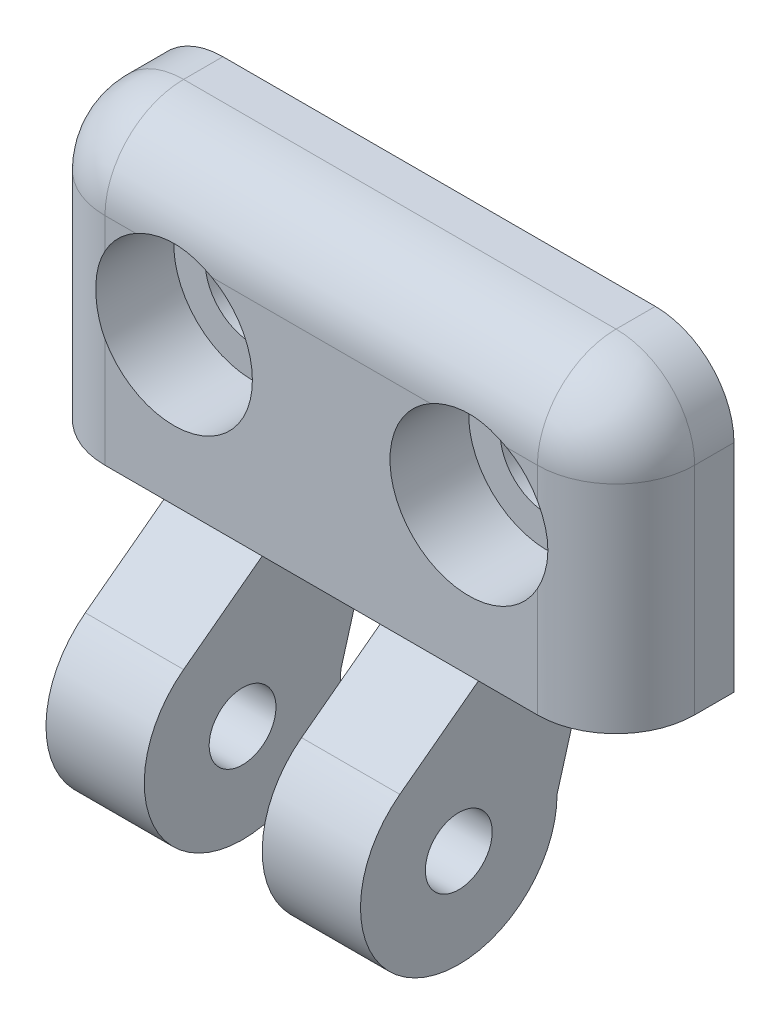
SolidWorks part; units mm, degrees
ref_plane "Front Plane" through (0, 0, 0) normal (0, 0, 1) x (1, 0, 0)
ref_plane "Top Plane" through (0, 0, 0) normal (0, 1, 0) x (1, 0, 0)
ref_plane "Right Plane" through (0, 0, 0) normal (1, 0, 0) x (0, 0, -1)
sketch "Sketch2" plane through (0, 0, 0) normal (0, 0, 1) x (1, 0, 0)
  line L1 (0, 0) -> (30, 0)
  line L2 (0, 0) -> (0, 15)
  line L3 (0, 15) -> (30, 15)
  line L4 (30, 0) -> (30, 15)
  dimension "D1" = 15
  dimension "D2" = 30
extrude "Boss-Extrude1" add sketch "Sketch2" along normal blind 6
hole_wizard "CBORE for M4 SHCS1" positions "Sketch3" profile "Sketch4" counterbore size "M4" standard "ANSI Metric" end condition through all
sketch "Sketch3" plane through (0, 0, 6) normal (0, 0, 1) x (1, 0, 0)
  line L0 (0, 15) -> (0, 0) construction
  line L1 (0, 0) -> (30, 0) construction
  point P0 (7.5, 7.5)
  point P2 (22.5, 7.5)
  dimension "D1" = 15
  dimension "D2" = 7.5
  dimension "D3" = 7.5
sketch "Sketch4" plane through (7.5, 7.5, 6) normal (1, 0, 0) x (0, -1, 0)
  line L0 (0, 0) -> (0, 6)
  line L1 (0, 6) -> (2.4, 6)
  line L3 (2.4, 6) -> (2.4, 4)
  line L4 (2.4, 4) -> (4, 4)
  line L5 (4, 4) -> (4, 0)
  line L7 (4, 0) -> (0, 0)
  line L11 (0, -6.35) -> (0, 107.95) construction
  dimension "Thru Hole Dia." = 4.8
  dimension "Thru Hole Depth" = 6
  dimension "C'Bore Dia." = 8
  dimension "C'Bore Depth" = 4
sketch "Sketch5" plane through (30, 0, 0) normal (1, 0, 0) x (0, 0, -1)
  line L0 (0, 0) -> (0, 15) construction
  line L1 (-6, 0) -> (0, 0) construction
  line L2 (0, 0) -> (-2, -7)
  line L3 (0, 0) -> (-6, 0)
  line L4 (-6, 0) -> (-10, -3)
  arc A0 (-10, -3) -> (-2, -7) centre (-7, -7) ccw
  dimension "D3" = 10
  dimension "D1" = 7
  dimension "D2" = 7
extrude "Boss-Extrude2" add sketch "Sketch5" against normal up to surface (30 mm away) up to face at (0, 7.5, 3)
sketch "Sketch6" plane through (0, 15, 0) normal (0, 1, 0) x (1, 0, 0)
  line L1 (18, -13.7315) -> (12, -13.7315)
  line L2 (18, -13.7315) -> (18, 4.2995)
  line L3 (18, 4.2995) -> (12, 4.2995)
  line L4 (12, -13.7315) -> (12, 4.2995)
  line L9 (7, -14.6057) -> (-9.2825, -14.6057)
  line L10 (7, -14.6057) -> (7, 3.316)
  line L11 (7, 3.316) -> (-9.2825, 3.316)
  line L12 (-9.2825, -14.6057) -> (-9.2825, 3.316)
  line L13 (30, -16.1356) -> (23, -16.1356)
  line L14 (30, -16.1356) -> (30, 4.2995)
  line L15 (30, 4.2995) -> (23, 4.2995)
  line L16 (23, -16.1356) -> (23, 4.2995)
  line L17 (30, -6) -> (30, -10) construction
  dimension "D1" = 6
  dimension "D2" = 7
  dimension "D3" = 17.9217
  dimension "D4" = 7
  dimension "D5" = 5
  dimension "D6" = 5
  dimension "D7" = 7
extrude "Cut-Extrude1" cut sketch "Sketch6" against normal through all from vertex starting at point (30, 0, 6)
sketch "Sketch7" plane through (7, 0, 0) normal (-1, 0, 0) x (0, 0, 1)
  circle A0 centre (7, -7) radius 1.7
  dimension "D1" = 3.4
extrude "Cut-Extrude2" cut sketch "Sketch7" against normal through all both and the other way through all
fillet "Fillet1" radius 4 5 edges at (0, 7.5, 6) (0, 15, 3) (30, 15, 3) (30, 7.5, 6) (15, 15, 6)
